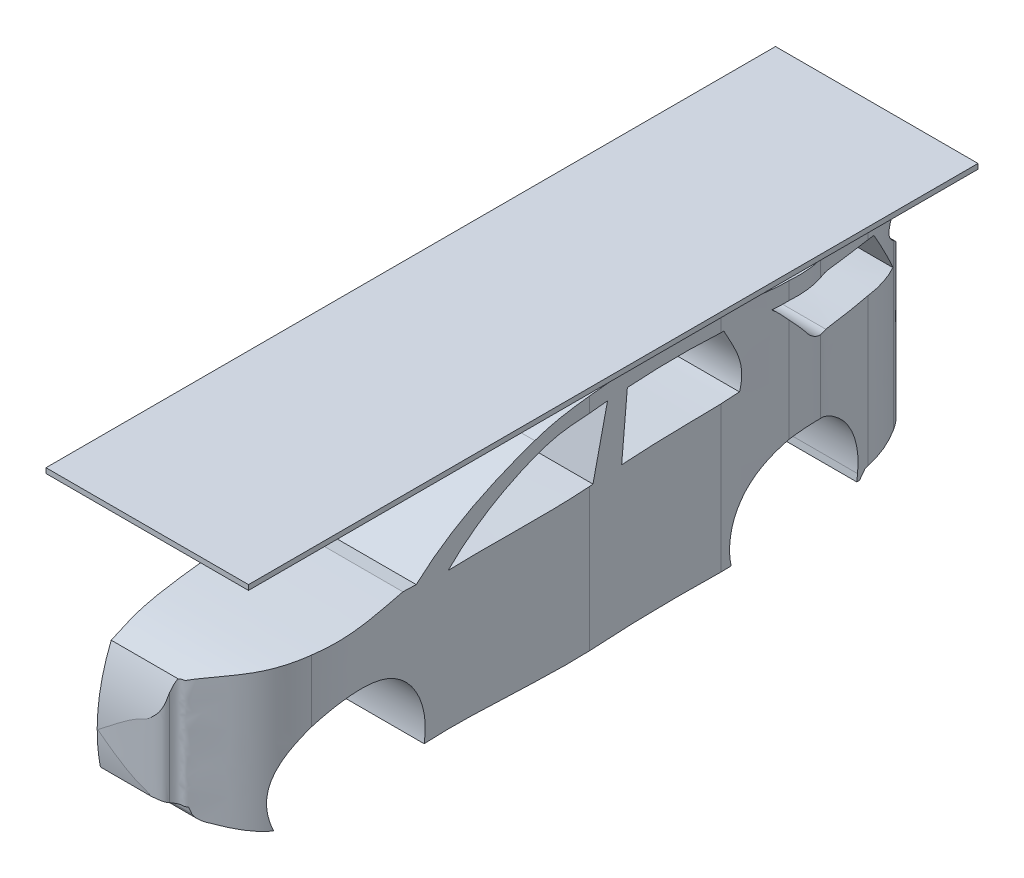
SolidWorks part; units mm, degrees
ref_plane "정면" through (0, 0, 0) normal (0, 0, 1) x (1, 0, 0)
ref_plane "윗면" through (0, 0, 0) normal (0, 1, 0) x (1, 0, 0)
ref_plane "우측면" through (0, 0, 0) normal (1, 0, 0) x (0, 0, -1)
sketch "스케치1" plane through (0, 0, 0) normal (1, 0, 0) x (0, 0, -1)
  line L1 (-750, -400) -> (750, -400)
  line L2 (-750, -400) -> (-750, 400)
  line L3 (-750, 400) -> (750, 400)
  line L4 (750, -400) -> (750, 400)
  line L5 (-750, -400) -> (750, 400) construction
  line L6 (-750, 400) -> (750, -400) construction
  point P0 (0, 0)
  dimension "D1" = 1500
  dimension "D2" = 800
extrude "보스-돌출1" add sketch "스케치1" along normal blind 200 and the other way blind 200
sketch "스케치2" plane through (200, 0, 0) normal (1, 0, 0) x (0, 0, -1)
  line L0 (-327.0655, -174.4796) -> (280.3017, -174.4796)
  line L9 (569.4102, -166.0763) -> (669.8489, -152.4149)
  line L10 (-373.0375, 110.4407) -> (-343.9029, 106.7988)
  line L11 (281.4336, 234.034) -> (340.9696, 132.9892)
  line L12 (340.9696, 132.9892) -> (338.5492, 128.0997)
  line L13 (32.9205, 233.3484) -> (2.548, 106.8677)
  line L14 (73.8074, 234.6644) -> (62.0974, 108.6765)
  line L15 (355.1965, 228.5849) -> (590.959, 221.4252)
  line L16 (590.959, 221.4252) -> (650.9165, 125.0753)
  line L17 (552.2142, -163.5539) -> (550.4432, -176.8766)
  line L18 (550.4432, -176.8766) -> (556.9508, -177.7416)
  line L19 (556.9508, -177.7416) -> (569.4102, -166.0763)
  line L20 (-750, 400) -> (750, 400)
  line L21 (-750, 400) -> (750, 400)
  line L22 (-750, 400) -> (-750, -400)
  line L23 (-750, -400) -> (750, -400)
  line L24 (750, 400) -> (750, -400)
  line L25 (-750, 400) -> (-750, -400)
  line L26 (-750, -400) -> (750, -400)
  line L27 (750, 400) -> (750, -400)
  arc A0 (-327.0655, -174.4796) -> (-602.8022, -196.5516) centre (-467.8797, -148.7145) ccw
  arc A1 (552.2142, -163.5539) -> (280.3017, -174.4796) centre (415.3072, -145.3549) ccw
  spline S0 degree 3 poles (-685.004, 51.5709) (-626.4182, 77.4027) (-628.6816, 85.697) (-373.0375, 110.4407) knots 0 0 0 0 1 1 1 1
  spline S1 degree 2 poles (-685.004, 51.5709) (-726.0089, -48.9386) (-706.4598, -154.5983) knots 0 0 0 1 1 1
  spline S2 degree 2 poles (-706.4598, -154.5983) (-693.5297, -161.3395) (-679.2965, -163.5539) knots 0 0 0 1 1 1
  spline S3 degree 1 poles (-679.2965, -163.5539) (-676.497, -174.4796) knots 0 0 1 1
  spline S4 degree 2 poles (-676.497, -174.4796) (-673.7605, -182.7229) (-665.2188, -186.1494) knots 0 0 0 1 1 1
  spline S5 degree 2 poles (-665.2188, -186.1494) (-635.016, -196.0947) (-602.8022, -196.5516) knots 0 0 0 1 1 1
  spline S7 degree 3 poles (669.8489, -152.4149) (680.3288, -150.7328) (693.6553, -146.6337) (712.3751, -130.6702) (720.9385, -117.1844) (729.8224, -105.5361) (719.2755, -86.7732) (724.8069, -56.239) (724.9856, -27.1522) (717.8742, -13.0614) knots 0 0 0 0 0.175584 0.216535 0.388067 0.416588 0.480301 0.7168 1 1 1 1
  spline S8 degree 3 poles (717.8742, -13.0614) (702.4767, -0.6243) (718.9173, 7.7414) (715.7815, 19.8681) knots 0 0 0 0 1 1 1 1
  spline S9 degree 3 poles (715.7815, 19.8681) (712.6763, 36.8726) (720.2731, 66.1248) (702.3012, 122.0428) (668.9964, 155.9424) (627.9863, 191.6079) (641.4143, 214.9058) (654.1986, 220.2774) (654.3336, 231.4512) (561.9766, 229.5734) (544.1476, 256.7603) (458.8364, 257.8015) knots 0 0 0 0 0.117399 0.199654 0.387439 0.462215 0.518073 0.539083 0.546387 0.58687 1 1 1 1
  spline S10 degree 2 poles (-343.9029, 106.7988) (-236.8817, 188.9621) (-112.2085, 238.4933) knots 0 0 0 1 1 1
  spline S11 degree 3 poles (-112.2085, 238.4933) (-54.5779, 262.4107) (45.7388, 262.7951) (145.3524, 266.3769) (184.8056, 266.1723) knots 0 0 0 0 0.605273 1 1 1 1
  spline S12 degree 2 poles (184.8056, 266.1723) (321.9901, 267.1519) (458.8364, 257.8015) knots 0 0 0 1 1 1
  spline S13 degree 3 poles (-278.1126, 96.8611) (-234.8798, 139.5862) (-164.4627, 190.5627) (-73.1996, 227.7149) (-9.7487, 231.8197) (36.3272, 233.5453) (163.9032, 237.3861) (264.7674, 237.6116) (355.1965, 228.5849) knots 0 0 0 0 0.268355 0.38868 0.430559 0.551187 0.594679 1 1 1 1
  spline S14 degree 3 poles (355.1965, 228.5849) (364.6314, 221.1589) (386.522, 197.0531) (409.1721, 173.7287) (422.2806, 157.8375) knots 0 0 0 0 0.367445 1 1 1 1
  spline S15 degree 3 poles (477.7635, 126.5188) (474.973, 126.1793) (453.4471, 126.4763) (432.5232, 143.2565) (422.2806, 157.8375) knots 0 0 0 0 0.128765 1 1 1 1
  spline S16 degree 3 poles (477.7635, 126.5188) (550.9367, 123.3386) (624.6896, 130.8971) (697.5705, 120.7037) knots 0 0 0 0 1 1 1 1
  spline S17 degree 3 poles (-278.1126, 96.8611) (-143.7745, 100.7095) (40.7303, 110.3274) (246.0019, 111.3071) (318.151, 116.7959) (338.5492, 128.0997) knots 0 0 0 0 0.65432 0.889445 1 1 1 1
  spline S18 degree 3 poles (265.7148, 234.7462) (284.5237, 197.9913) (310.4724, 164.1701) (296.169, 115.6847) knots 0 0 0 0 1 1 1 1
  point P0 (-685.004, 51.5709)
  point P1 (-373.0375, 110.4407)
  point P2 (-343.9029, 106.7988)
  point P14 (-685.004, 51.5709)
  point P26 (-327.0655, -174.4796)
  point P97 (-687.2146, 47.7034)
  point P98 (0, 0)
  point P99 (-633.6084, 70.0709)
  point P100 (-639.7647, 71.123)
  line M13 (750, -400) -> (750, 400)
  line M14 (750, 400) -> (-750, 400)
  line M15 (-750, 400) -> (-750, -400)
  line M16 (-750, -400) -> (750, -400)
extrude "컷-돌출1" cut sketch "스케치2" against normal through all both and the other way through all contours S11 S12 S9 S8 S7 L9 L19 L18 L17 A1 L0 A0 S5 S4 S3 S2 S1 S0 L10 S10 M16 M13 M14 M15 | S13 S17 L13 | S18 S13 L14 S17 | S15 S16 L16 L15 S14 region at (200, 176.8095, -510.8443) region at (200, 171.425, -178.3937) region at (200, 156.9512, 94.9749) region at (200, 383, 0)
ref_plane "평면1" through (0, 300, 0) normal (0, 1, 0) x (1, 0, 0)
sketch "스케치3" plane through (0, 300, 0) normal (0, 1, 0) x (1, 0, 0)
  line L1 (-200, -712.771) -> (200, -712.771)
  line L2 (-200, -712.771) -> (-200, 728.2572)
  line L3 (-200, 728.2572) -> (200, 728.2572)
  line L4 (200, -712.771) -> (200, 728.2572)
extrude "보스-돌출2" add sketch "스케치3" along normal blind 10 separate body
sketch "스케치5" plane through (0, 310, 0) normal (0, 1, 0) x (1, 0, 0)
  line L0 (-98.9136, 721.9586) -> (-98.9136, -999.4181) construction
  line L1 (-200, -712.771) -> (200, -712.771) construction
  line L2 (-98.9136, 721.9586) -> (-98.9136, -712.771)
  line L4 (-200, 728.2572) -> (200, 728.2572)
  line L5 (-200, 728.2572) -> (-200, -712.771)
  line L6 (-200, -712.771) -> (200, -712.771)
  line L7 (200, 728.2572) -> (200, -712.771)
  spline S0 degree 2 poles (-98.9136, 721.9586) (-19.9658, 720.5172) (55.025, 696.0724) knots 0 0 0 1 1 1
  spline S1 degree 2 poles (55.025, 696.0724) (89.5724, 685.3591) (107.3977, 654.0025) knots 0 0 0 1 1 1
  spline S2 degree 2 poles (107.3977, 654.0025) (128.6584, 618.6846) (133.6649, 577.3452) knots 0 0 0 1 1 1
  spline S3 degree 3 poles (133.6649, 577.3452) (139.0891, 549.2694) (144.1478, 510.8515) (150.386, 471.769) (155.6472, 461.5572) knots 0 0 0 0 0.714493 1 1 1 1
  spline S4 degree 2 poles (155.6472, 461.5572) (167.2498, 426.3678) (165.6174, 389.3828) knots 0 0 0 1 1 1
  spline S5 degree 3 poles (165.6174, 389.3828) (167.9264, 345.9191) (158.2979, 302.9627) (160.7391, 259.5487) knots 0 0 0 0 1 1 1 1
  spline S6 degree 2 poles (160.7391, 259.5487) (157.5394, 127.0501) (165.6174, -5.0814) knots 0 0 0 1 1 1
  spline S7 degree 3 poles (165.6174, -5.0814) (170.0912, -120.8493) (142.7942, -304.2776) (184.3243, -485.3841) (163.2084, -551.3858) knots 0 0 0 0 0.635961 1 1 1 1
  spline S8 degree 3 poles (163.2084, -551.3858) (157.1186, -573.5909) (131.6356, -626.0374) (82.6407, -654.7843) (49.7761, -677.7738) (41.4072, -684.9087) (33.2346, -681.3738) (24.9193, -693.8186) knots 0 0 0 0 0.360199 0.838601 0.896483 0.934297 1 1 1 1
  spline S9 degree 3 poles (24.9193, -693.8186) (22.1816, -701.4886) (10.0844, -704.8466) (-4.541, -707.3929) (-38.194, -709.631) (-64.3574, -712.8335) (-98.9136, -712.771) knots 0 0 0 0 0.174631 0.264685 0.347221 1 1 1 1
  point P39 (167.9391, -2.9716)
  point P40 (163.5277, -4.8896)
  point P41 (165.6174, -5.0814)
ref_plane "평면2" through (0, 62.7602, 0) normal (0, 1, 0) x (1, 0, 0)
sketch "스케치8" plane through (0, 62.7602, 0) normal (0, 1, 0) x (1, 0, 0)
  line L0 (-98.9136, 721.9586) -> (-98.9136, -999.4181) construction
  line L2 (-98.9136, 721.9586) -> (-98.9136, -712.771)
  line L4 (-200, 728.2572) -> (200, 728.2572)
  line L5 (-200, 728.2572) -> (-200, -712.771)
  line L6 (-200, -712.771) -> (200, -712.771)
  line L7 (200, 728.2572) -> (200, -712.771)
  spline S0 degree 2 poles (-98.9136, 721.9586) (-19.9658, 720.5172) (55.025, 696.0724) knots 0 0 0 1 1 1
  spline S1 degree 2 poles (55.025, 696.0724) (89.5724, 685.3591) (107.3977, 654.0025) knots 0 0 0 1 1 1
  spline S2 degree 2 poles (107.3977, 654.0025) (128.6584, 618.6846) (133.6649, 577.3452) knots 0 0 0 1 1 1
  spline S3 degree 3 poles (133.6649, 577.3452) (139.0891, 549.2694) (144.1478, 510.8515) (150.386, 471.769) (155.6472, 461.5572) knots 0 0 0 0 0.714493 1 1 1 1
  spline S4 degree 2 poles (155.6472, 461.5572) (167.2498, 426.3678) (165.6174, 389.3828) knots 0 0 0 1 1 1
  spline S5 degree 3 poles (165.6174, 389.3828) (167.9264, 345.9191) (158.2979, 302.9627) (160.7391, 259.5487) knots 0 0 0 0 1 1 1 1
  spline S6 degree 2 poles (160.7391, 259.5487) (157.5394, 127.0501) (165.6174, -5.0814) knots 0 0 0 1 1 1
  spline S7 degree 3 poles (165.6174, -5.0814) (170.0912, -120.8493) (142.7942, -304.2776) (184.3243, -485.3841) (163.2084, -551.3858) knots 0 0 0 0 0.635961 1 1 1 1
  spline S8 degree 3 poles (163.2084, -551.3858) (157.1186, -573.5909) (131.6356, -626.0374) (82.6407, -654.7843) (49.7761, -677.7738) (41.4072, -684.9087) (33.2346, -681.3738) (24.9193, -693.8186) knots 0 0 0 0 0.360199 0.838601 0.896483 0.934297 1 1 1 1
  spline S9 degree 3 poles (24.9193, -693.8186) (22.1816, -701.4886) (10.0844, -704.8466) (-4.541, -707.3929) (-38.194, -709.631) (-64.3574, -712.8335) (-98.9136, -712.771) knots 0 0 0 0 0.174631 0.264685 0.347221 1 1 1 1
  point P39 (167.9391, -2.9716)
  point P40 (163.5277, -4.8896)
  point P41 (165.6174, -5.0814)
extrude "컷-돌출3" cut sketch "스케치8" against normal through all both and the other way through all contours S8 S9 L6 L7 L4 L5 L2 S0 S1 S2 S3 S4 S5 S6 S7 region at (-113.8687, 62.7602, -4.5938)
